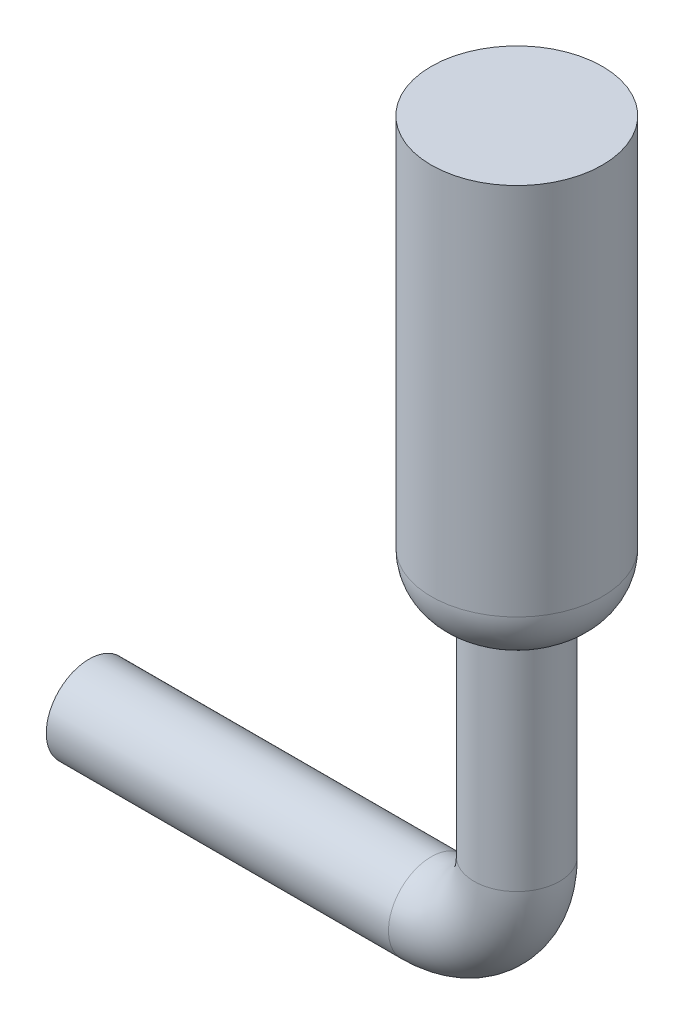
SolidWorks part; units mm, degrees
ref_plane "Front Plane" through (0, 0, 0) normal (0, 0, 1) x (1, 0, 0)
ref_plane "Top Plane" through (0, 0, 0) normal (0, 1, 0) x (1, 0, 0)
ref_plane "Right Plane" through (0, 0, 0) normal (1, 0, 0) x (0, 0, -1)
sketch "Sketch1" plane through (0, 0, 0) normal (0, 0, 1) x (1, 0, 0)
  line L0 (-25.4, 0) -> (-127, 0)
  line L1 (0, 25.4) -> (0, 88.9)
  arc A0 (0, 25.4) -> (-25.4, 0) centre (-25.4, 25.4) cw
  point P6 (0, 0)
  dimension "D3" = 25.4
  dimension "D1" = 88.9
  dimension "D2" = 127
ref_plane "Plane1" through (0, 88.9, 0) normal (0, 1, 0) x (1, 0, 0)
ref_plane "Plane2" through (-127, 0, 0) normal (1, 0, 0) x (0, 0, -1)
sketch "Sketch2" plane through (0, 88.9, 0) normal (0, 1, 0) x (1, 0, 0)
  circle A0 centre (0, 0) radius 25.4
  dimension "D1" = 50.8
sketch "Sketch3" plane through (-127, 0, 0) normal (1, 0, 0) x (0, 0, -1)
  circle A0 centre (0, 0) radius 12.7
  dimension "D1" = 25.4
sweep "Sweep1" add path "Sketch1" circular profile diameter 25.4 parameters "D3"=25.4
extrude "Boss-Extrude1" add sketch "Sketch2" along normal blind 127 contours A0
fillet "Fillet1" radius 16.51 1 edges at (0, 88.9, 25.4)
